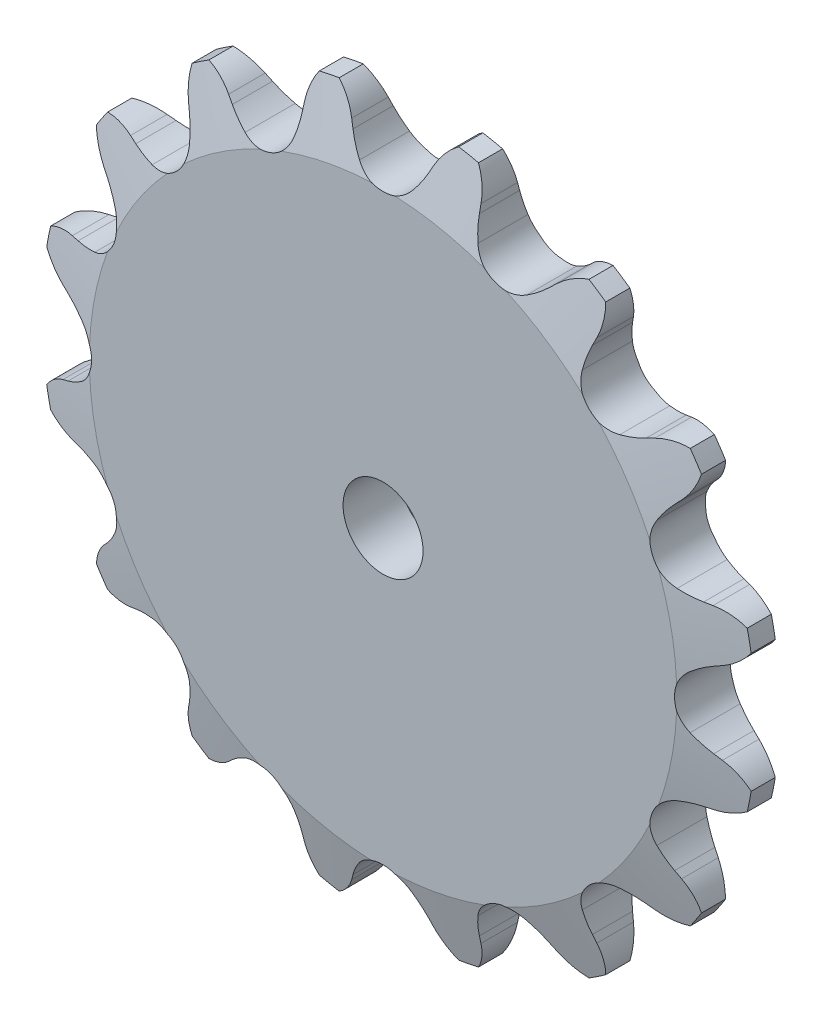
SolidWorks part; units mm, degrees
ref_plane "Front Plane" through (0, 0, 0) normal (0, 0, 1) x (1, 0, 0)
ref_plane "Top Plane" through (0, 0, 0) normal (0, 1, 0) x (1, 0, 0)
ref_plane "Right Plane" through (0, 0, 0) normal (1, 0, 0) x (0, 0, -1)
ref_axis "Axis1" through (0, 0, -88.99) along (0, 0, 1)
sketch "Sprocket-BaseSketch" plane through (0, 0, 0) normal (1, 0, 0) x (0, 0, -1)
  line L0 (1.397, 0) -> (1.397, 14.6918)
  line L1 (1.397, 14.6918) -> (0.6032, 17.8668)
  line L2 (0.6032, 17.8668) -> (-0.6032, 17.8668)
  line L3 (-0.6032, 17.8668) -> (-1.397, 14.6918)
  line L4 (-1.397, 14.6918) -> (-1.397, 0)
  line L5 (-1.397, 0) -> (1.397, 0)
  line L6 (5.588, 0) -> (-1.7463, 0) construction
  dimension "Hub Surface" = 1.397
  dimension "RightSide (1)" = 0.7938
  dimension "RightSide (2)" = 3.175
  dimension "OD" = 17.8668
  dimension "LeftSide (1)" = 0.7938
  dimension "LeftSide (2)" = 3.175
  dimension "Tooth Width" = 2.794
revolve "25 (04C) ANSI (ISO) Chain Number, 1.281in P.D." add sketch "Sprocket-BaseSketch" angle 360 about L6
sketch "Tooth-Sketch" plane through (0, 0, 0) normal (0, 0, 1) x (1, 0, 0)
  line L0 (0, 0) -> (0, 21.6994) construction
  line L1 (1.896, 16.1459) -> (2.0514, 16.491)
  line L2 (-1.896, 16.1459) -> (-2.0514, 16.491)
  line L3 (0, 16.2745) -> (6.228, 15.0357) construction
  line L4 (0, 16.2745) -> (-6.228, 15.0357) construction
  arc A0 (-1.3237, 15.2121) -> (1.3237, 15.2121) centre (0, 16.2745) ccw
  arc A1 (1.3237, 15.2121) -> (1.896, 16.1459) centre (-2.0601, 17.928) ccw
  arc A2 (-1.3237, 15.2121) -> (-1.896, 16.1459) centre (2.0601, 17.928) cw
  arc A3 (2.0514, 16.491) -> (4.534, 18.0955) centre (4.534, 15.3726) cw
  arc A4 (-2.0514, 16.491) -> (-4.534, 18.0955) centre (-4.534, 15.3726) ccw
  arc A5 (4.534, 18.0955) -> (-4.534, 18.0955) centre (0, 0) ccw
extrude "Tooth-Cut, Number of teeth: 16" cut sketch "Tooth-Sketch" against normal through all and the other way through all
pattern_circular "Tooth Pattern, 16 / 16" count 16 every 22.5 about axis through (0, 0, -88.99) along (0, 0, 1) of "Tooth-Cut, Number of teeth: 16"
sketch "Sketch4" plane through (0, 0, 0) normal (0, 0, 1) x (1, 0, 0)
  circle A0 centre (0, 0) radius 2
  dimension "D1" = 4
extrude "Cut-Extrude1" cut sketch "Sketch4" against normal through all and the other way through all
sketch "Sketch5" plane through (0, 0, 0) normal (0, 0, 1) x (1, 0, 0)
  circle A0 centre (0, 0) radius 17.8668
  dimension "D1" = 35.7336
equation "\"D1@Sketch5\" = \"OD@Sprocket-BaseSketch\"*2"
